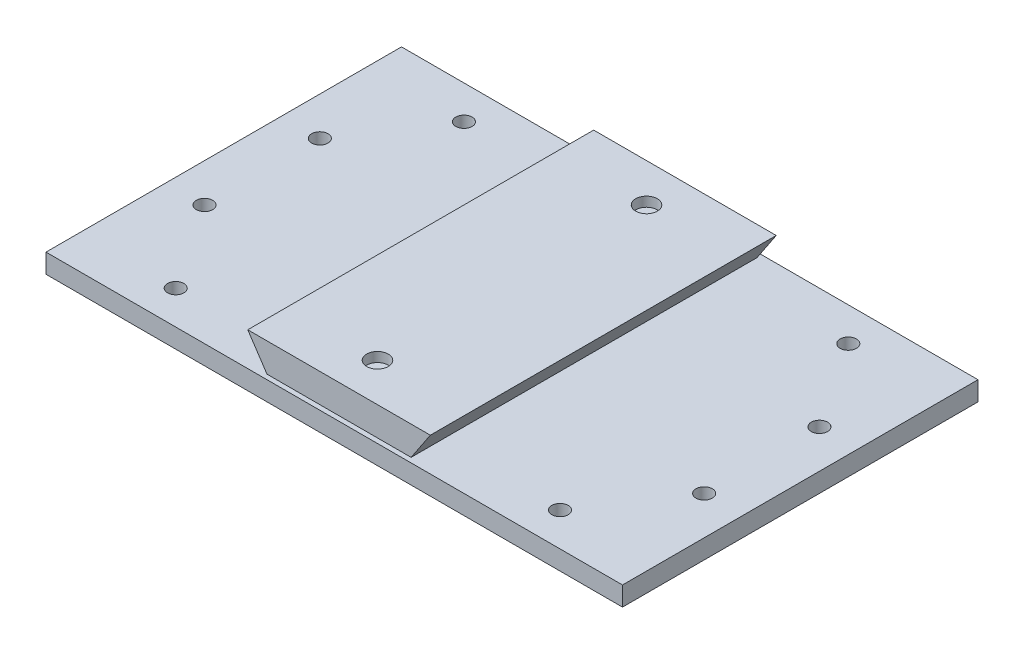
SolidWorks part; units mm, degrees
ref_plane "Front Plane" through (0, 0, 0) normal (0, 0, 1) x (1, 0, 0)
ref_plane "Top Plane" through (0, 0, 0) normal (0, 1, 0) x (1, 0, 0)
ref_plane "Right Plane" through (0, 0, 0) normal (1, 0, 0) x (0, 0, -1)
sketch "Sketch1" plane through (0, 0, 0) normal (0, 1, 0) x (1, 0, 0)
  line L1 (-60, -37) -> (60, -37)
  line L2 (-60, -37) -> (-60, 37)
  line L3 (-60, 37) -> (60, 37)
  line L4 (60, -37) -> (60, 37)
extrude "Rail Plate" add sketch "Sketch1" along normal blind 4
sketch "Sketch2" plane through (0, 0, 0) normal (0, 0, 1) x (1, 0, 0)
  line L0 (-14.6667, 3.5) -> (14.6667, 3.5)
  line L1 (14.6667, 3.5) -> (19, 10)
  line L2 (19, 10) -> (-19, 10)
  line L3 (-19, 10) -> (-14.6667, 3.5)
extrude "Dovetail Rail" add sketch "Sketch2" along normal mid plane 72
ref_plane "Rail Face" through (0, 10, 0) normal (0, 1, 0) x (1, 0, 0)
sketch "Sketch3" plane through (0, 10, 0) normal (0, 1, 0) x (1, 0, 0)
  circle A0 centre (0, -28) radius 2.25
  circle A1 centre (0, 28) radius 2.25
extrude "Lock Detents" cut sketch "Sketch3" against normal blind 2
sketch "Sketch4" plane through (0, 0, 0) normal (0, 1, 0) x (1, 0, 0)
  circle A0 centre (-40, -30) radius 1.7
  circle A1 centre (-40, 30) radius 1.7
  circle A2 centre (40, -30) radius 1.7
  circle A3 centre (40, 30) radius 1.7
  circle A4 centre (-52, -12) radius 1.7
  circle A5 centre (-52, 12) radius 1.7
  circle A6 centre (52, -12) radius 1.7
  circle A7 centre (52, 12) radius 1.7
extrude "Bolt Holes" cut sketch "Sketch4" against normal through all and the other way through all
equation "\"PlateW\" = 120.0"
equation "\"PlateH\" = 74.0"
equation "\"PlateT\" = 4.0"
equation "\"RailW\" = 30.0"
equation "\"RailW2\" = 38.0"
equation "\"RailH\" = 6.0"
equation "\"RailL\" = 72.0"
equation "\"DetentD\" = 4.5"
equation "\"DetentDepth\" = 2.0"
equation "\"DetentZ\" = 28.0"
equation "\"JoinL\" = 44.0"
equation "\"JoinW\" = 20.0"
equation "\"JoinT\" = 3.0"
equation "\"JoinPitch\" = 24.0"
equation "\"BoltD\" = 3.4"
